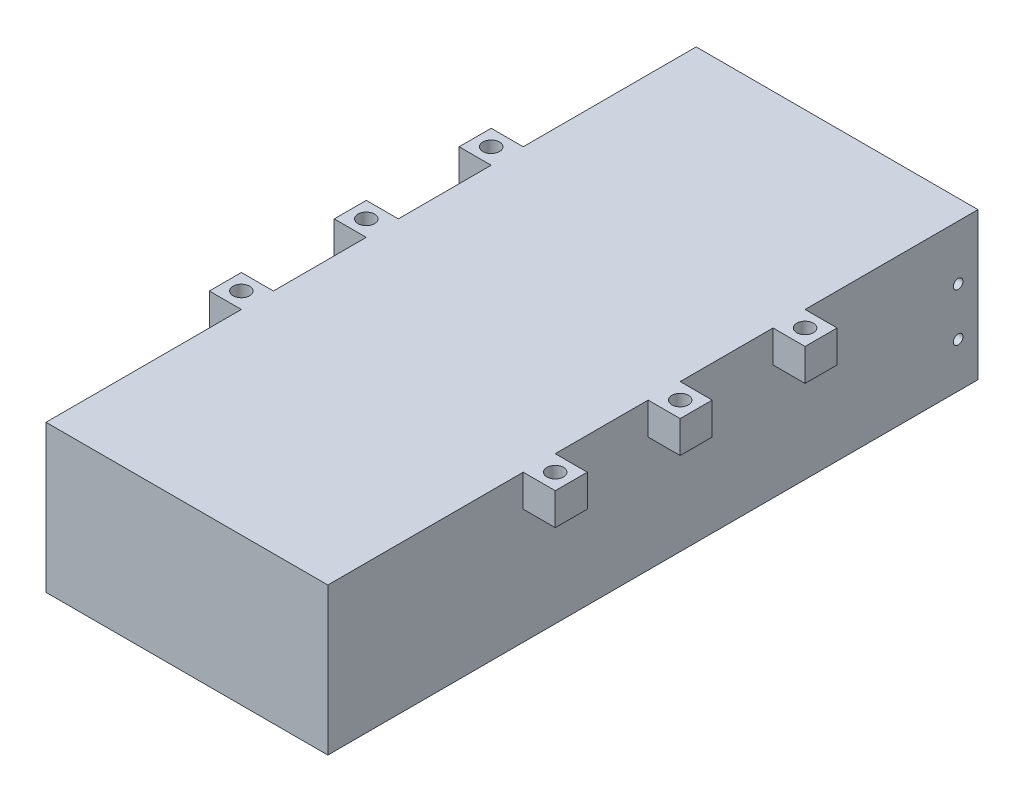
SolidWorks part; units mm, degrees
ref_plane "Front Plane" through (0, 0, 0) normal (0, 0, 1) x (1, 0, 0)
ref_plane "Top Plane" through (0, 0, 0) normal (0, 1, 0) x (1, 0, 0)
ref_plane "Right Plane" through (0, 0, 0) normal (1, 0, 0) x (0, 0, -1)
sketch "Sketch1" plane through (0, 0, 0) normal (0, 0, 1) x (1, 0, 0)
  line L0 (-44, 0) -> (-44, -3) construction
  line L1 (0, 0) -> (-88, 0)
  line L2 (0, 0) -> (0, -46)
  line L3 (0, -46) -> (-88, -46)
  line L4 (-88, 0) -> (-88, -46)
  line L5 (-44, -3) -> (-85, -3) construction
  line L7 (-85, -3) -> (-3, -3)
  line L8 (-85, -3) -> (-85, -43)
  line L9 (-85, -43) -> (-3, -43)
  line L10 (-3, -3) -> (-3, -43)
  dimension "D1" = 88
  dimension "D2" = 46
  dimension "D3" = 3
  dimension "D4" = 41
  dimension "D5" = 40
  dimension "D6" = 82
extrude "Boss-Extrude1" add sketch "Sketch1" along normal blind 3 contours L10 L7 L8 L9 | L1 L4 L3 L2 L7 L10 L9 L8 region at (-0.993, -23, 0) region at (-44, -23, 0)
sketch "Sketch3" plane through (0, 0, 0) normal (0, 0, -1) x (-1, 0, 0)
  line L0 (44, 0) -> (44, -3) construction
  line L1 (0, 0) -> (88, 0)
  line L2 (0, 0) -> (0, -46)
  line L3 (0, -46) -> (88, -46)
  line L4 (88, 0) -> (88, -46)
  line L5 (24, -3) -> (43, -3)
  line L6 (43, -1.5) -> (45, -1.5)
  line L7 (3, -3) -> (22, -3)
  line L8 (3, -3) -> (3, -43)
  line L9 (3, -43) -> (22, -43)
  line L10 (85, -3) -> (85, -43)
  line L11 (43, -1.5) -> (43, -3)
  line L12 (45, -1.5) -> (45, -3)
  line L13 (44, -1.5) -> (45, -1.5) construction
  line L14 (44, -1.5) -> (45, -1.507) construction
  line L15 (44, -1.5) -> (45, -1.5) construction
  line L16 (44, -1.5) -> (65, -1.5) construction
  line L17 (44, -1.5) -> (23, -1.5) construction
  line L18 (66, -1.5) -> (64, -1.5)
  line L19 (64, -1.5) -> (64, -3)
  line L20 (66, -1.5) -> (66, -3)
  line L21 (22, -1.5) -> (24, -1.5)
  line L22 (22, -1.5) -> (22, -3)
  line L23 (24, -1.5) -> (24, -3)
  line L24 (3, -23) -> (85, -23) construction
  line L25 (64, -44.5) -> (64, -43)
  line L26 (66, -44.5) -> (66, -43)
  line L27 (66, -44.5) -> (64, -44.5)
  line L28 (45, -44.5) -> (45, -43)
  line L29 (43, -44.5) -> (45, -44.5)
  line L30 (43, -44.5) -> (43, -43)
  line L31 (24, -44.5) -> (24, -43)
  line L32 (22, -44.5) -> (24, -44.5)
  line L33 (22, -44.5) -> (22, -43)
  line L34 (24, -43) -> (43, -43)
  line L35 (45, -43) -> (64, -43)
  line L36 (66, -43) -> (85, -43)
  line L37 (66, -3) -> (85, -3)
  line L38 (45, -3) -> (64, -3)
  line L39 (43, -3) -> (24, -3) construction
  line L40 (22, -3) -> (3, -3) construction
  point P15 (44, -1.5)
  point P24 (65, -1.5)
  point P29 (23, -1.5)
  dimension "D1" = 3
  dimension "D2" = 41
  dimension "D3" = 40
  dimension "D4" = 82
  dimension "D5" = 2
  dimension "D6" = 21
  dimension "D7" = 21
  dimension "D8" = 2
  dimension "D9" = 2
extrude "Boss-Extrude2" add sketch "Sketch3" along normal blind 200
sketch "Sketch4" plane through (0, 0, 0) normal (0, 1, 0) x (1, 0, 0)
  line L0 (0, 200) -> (0, 180) construction
  line L1 (0, -3) -> (0, 200) construction
  line L2 (0, 180) -> (0, 175) construction
  line L3 (0, 136) -> (10, 136)
  line L4 (0, 175) -> (10, 175) construction
  line L5 (0, 175) -> (0, 185) construction
  line L6 (0, 185) -> (10, 185) construction
  line L7 (10, 175) -> (10, 185) construction
  line L8 (0, 136) -> (0, 146)
  line L9 (10, 136) -> (10, 146)
  line L10 (0, 146) -> (10, 146)
  line L11 (0, 97) -> (10, 97)
  line L12 (0, 97) -> (0, 107)
  line L13 (10, 97) -> (10, 107)
  line L14 (0, 107) -> (10, 107)
  line L15 (0, 58) -> (10, 58)
  line L16 (0, 58) -> (0, 68)
  line L17 (10, 58) -> (10, 68)
  line L18 (0, 68) -> (10, 68)
  line L23 (-44, 200) -> (-44, -3) construction
  line L24 (-88, 200) -> (0, 200) construction
  line L25 (0, -3) -> (-88, -3) construction
  line L30 (-98, 136) -> (-98, 146)
  line L31 (-88, 136) -> (-98, 136)
  line L32 (-88, 146) -> (-98, 146)
  line L33 (-88, 136) -> (-88, 146)
  line L34 (-98, 97) -> (-98, 107)
  line L35 (-88, 97) -> (-98, 97)
  line L36 (-88, 97) -> (-88, 107)
  line L37 (-88, 107) -> (-98, 107)
  line L38 (-88, 68) -> (-98, 68)
  line L39 (-98, 58) -> (-98, 68)
  line L40 (-88, 58) -> (-88, 68)
  line L41 (-88, 58) -> (-98, 58)
  line L46 (0, 19) -> (10, 19) [skipped]
  line L47 (10, 19) -> (10, 29) [skipped]
  line L48 (0, 29) -> (10, 29) [skipped]
  line L49 (0, 19) -> (0, 29) [skipped]
  dimension "D1" = 20
  dimension "D2" = 5
  dimension "D3" = 10
  dimension "D4" = 10
  dimension "D6" = 29
  dimension "D5" = 5
extrude "Boss-Extrude3" add sketch "Sketch4" against normal blind 10
sketch "Sketch7" plane through (0, 0, 0) normal (0, 1, 0) x (1, 0, 0)
  line L0 (-93, 146) -> (-93, 48.2933) construction
  line L1 (-88, 146) -> (-98, 146) construction
  line L2 (5, 146) -> (5, 47.5439) construction
  line L3 (10, 146) -> (0, 146) construction
  line L4 (-98, 141) -> (-93, 141) construction
  line L5 (-98, 146) -> (-98, 136) construction
  line L6 (-98, 102) -> (-93, 102) construction
  line L7 (-98, 107) -> (-98, 97) construction
  line L8 (-98, 63) -> (-93, 63) construction
  line L9 (-98, 68) -> (-98, 58) construction
  line L10 (10, 63) -> (5, 63) construction
  line L11 (10, 58) -> (10, 68) construction
  line L12 (10, 102) -> (5, 102) construction
  line L13 (10, 141) -> (5, 141) construction
  line L14 (10, 136) -> (10, 146) construction
  circle A0 centre (-93, 141) radius 2.6
  circle A1 centre (-93, 102) radius 2.6
  circle A2 centre (-93, 63) radius 2.6
  circle A3 centre (5, 141) radius 2.6
  circle A4 centre (5, 102) radius 2.6
  circle A5 centre (5, 63) radius 2.6
  dimension "D5" = 5.2
  dimension "D7" = 39
extrude "Cut-Extrude1" cut sketch "Sketch7" against normal through all
sketch "Sketch8" plane through (0, 0, -200) normal (0, 0, -1) x (-1, 0, 0)
  line L1 (88, -46) -> (88, 0) construction
  line L2 (85, -43) -> (85, -3) construction
  line L4 (85, -25.5) -> (88, -25.5)
  line L5 (85, -25.5) -> (85, -20.5)
  line L6 (85, -20.5) -> (88, -20.5)
  line L7 (88, -25.5) -> (88, -20.5)
  dimension "D1" = 5
extrude "Boss-Extrude4" add sketch "Sketch8" along normal blind 8
sketch "Sketch9" plane through (-88, 0, 0) normal (-1, 0, 0) x (0, 0, 1)
  line L1 (-208, -20.5) -> (-200, -20.5) construction
  line L3 (-208, -20.5) -> (-205.5, -20.5)
  line L4 (-204, -23) -> (-208, -23)
  line L5 (-208, -25.5) -> (-208, -20.5) construction
  circle A2 centre (-205.5, -23) radius 1.5
  dimension "D1" = 2.5
  dimension "D2" = 3
fillet "Fillet1" 2 edges at (-86.5, -20.5, -208) (-86.5, -25.5, -208) type full round first side face at (-86.5, -20.5, -204) second side face at (-86.5, -25.5, -204) middle face at (-86.5, -23, -208)
sketch "Sketch10" plane through (0, 0, 0) normal (1, 0, 0) x (0, 0, -1)
  line L0 (200, -23) -> (193.8, -23)
  line L1 (200, 0) -> (200, -46) construction
  line L2 (193.8, -23) -> (193.8, -32)
  circle A0 centre (193.8, -32) radius 1.5
  circle A1 centre (193.8, -17) radius 1.5
  dimension "D2" = 3
  dimension "D4" = 3
  dimension "D1" = 6.2
  dimension "D3" = 9
  dimension "D5" = 15
extrude "Cut-Extrude3" cut sketch "Sketch10" against normal blind 10 contours A1 | A0
extrude "Cut-Extrude4" cut sketch "Sketch9" against normal blind 10 contours A2
